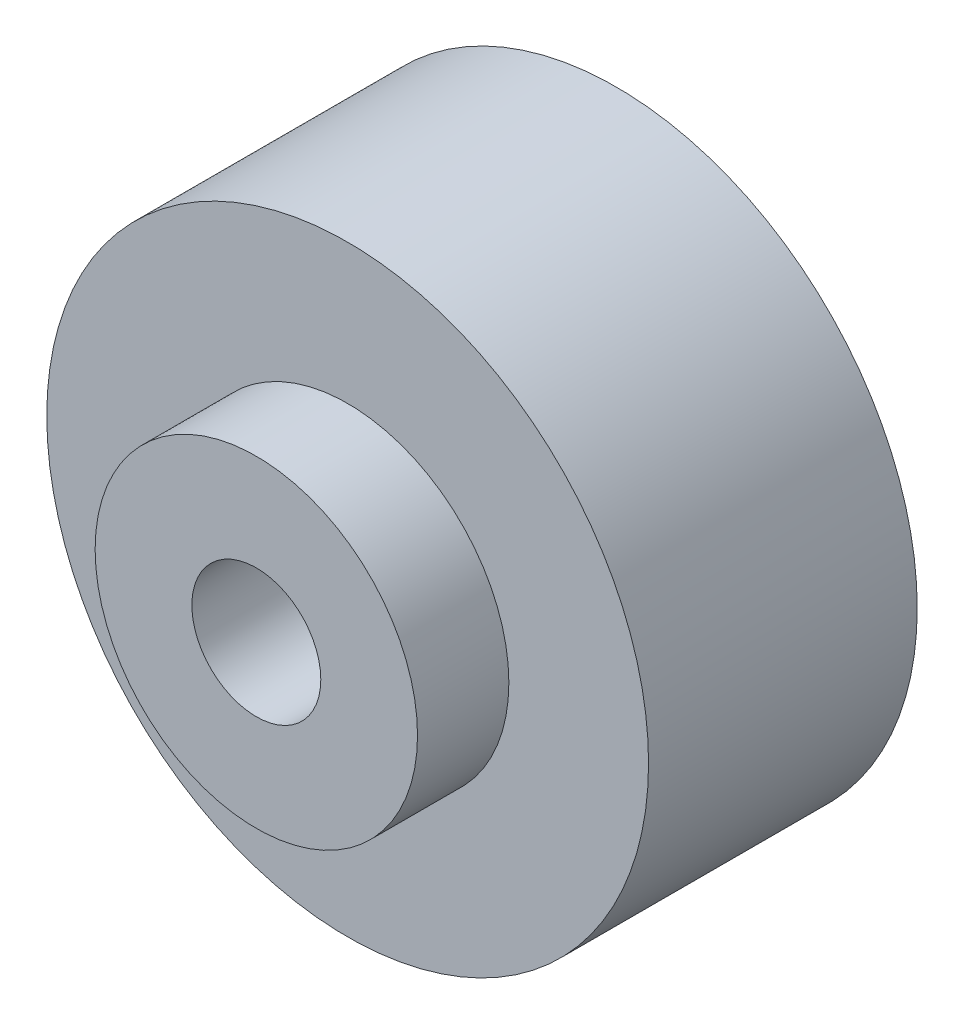
SolidWorks part; units mm, degrees
ref_plane "Front Plane" through (0, 0, 0) normal (0, 0, 1) x (1, 0, 0)
ref_plane "Top Plane" through (0, 0, 0) normal (0, 1, 0) x (1, 0, 0)
ref_plane "Right Plane" through (0, 0, 0) normal (1, 0, 0) x (0, 0, -1)
sketch "Sketch1" plane through (0, 0, 0) normal (0, 0, 1) x (1, 0, 0)
  circle A0 centre (0, 0) radius 6
  circle A1 centre (0, 0) radius 15
  circle A2 centre (0, 0) radius 28
  dimension "D1" = 12
  dimension "D2" = 30
  dimension "D3" = 56
extrude "Boss-Extrude1" add sketch "Sketch1" along normal blind 8.5 contours A1 A0 region at (-14.5757, 0, 0)
extrude "Boss-Extrude2" add sketch "Sketch1<3>" against normal blind 25 separate body contours A2 A1 | A1 A0 region at (-14.5757, 0, 0) region at (-27.208, 0, 0)
sketch "Sketch1<3>" plane through (0, 0, 0) normal (0, 0, 1) x (1, 0, 0) same geometry as "Sketch1"
equation "\"ShaftDiameter\"= 12mm"
equation "\"PendulumDiameter\"=12mm"
equation "\"PendulumLength\"= 140mm"
equation "\"EncoderOuterDiameter\"=1.5"
equation "\"EncoderShaftDiameter\"= 6mm"
equation "\"EncoderShaftLength\"=15mm+.5in+3mm"
equation "\"PendulumHolderangle\"=60"
equation "\"PendulumholderBottomHeight\"= 75"
equation "\"PendulumholderBottomWidth\"= 75"
equation "\"PendulumholderHeight\"=25"
equation "\"BearingOutsideDiameter\"=21mm"
equation "\"PendulumHolderWidth\"= 100mm"
equation "\"ShaftHeightFromTSlot\"= 100mm"
equation "\"BearingThickness\"= 5mm"
equation "\"D1@Sketch1\"=\"ShaftDiameter\""
equation "\"SlipRingOuterDiameter\"=56mm"
equation "\"D3@Sketch1\"=\"SlipRingOuterDiameter\""
equation "\"SlipringSmallThickness\"=8.5mm"
equation "\"D1@Boss-Extrude1\"=\"SlipringSmallThickness\""
equation "\"SlipringBigThickness\"=25mm"
equation "\"SlipringThickness\"= \"SlipringSmallThickness\" + \"SlipringBigThickness\""
